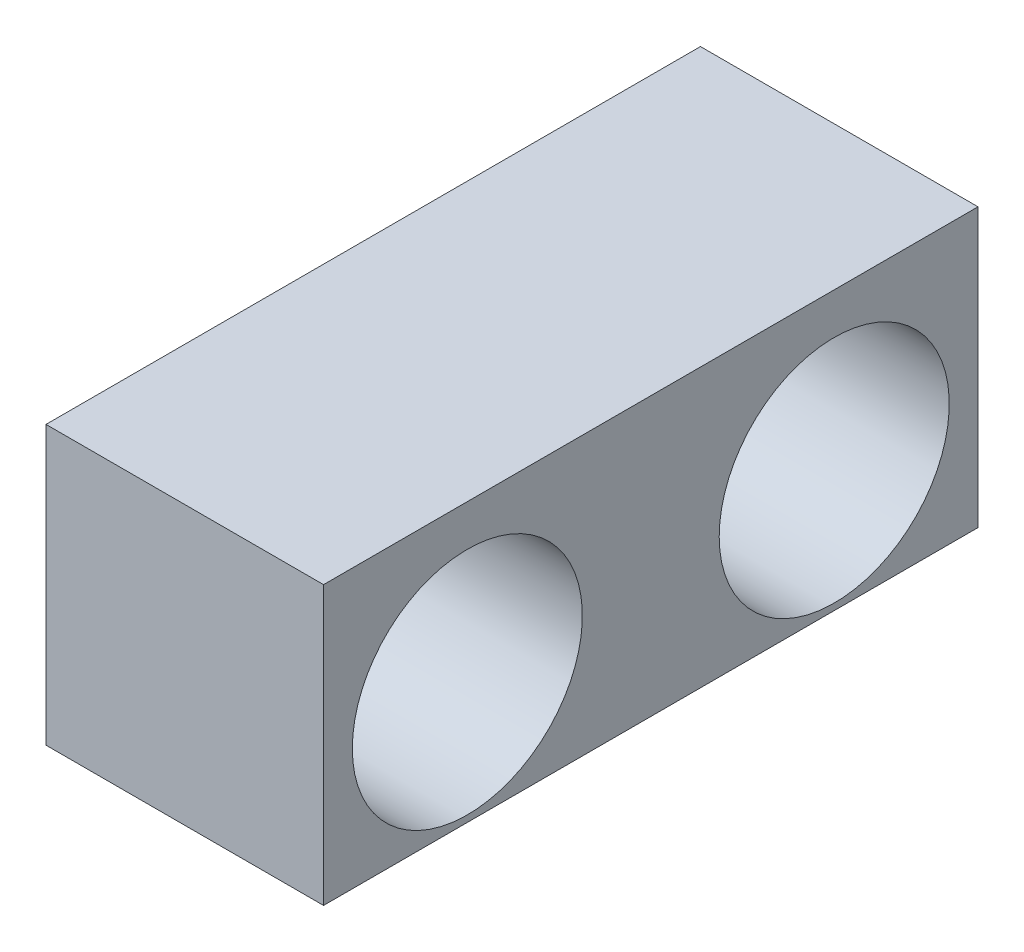
SolidWorks part; units mm, degrees
ref_plane "Front Plane" through (0, 0, 0) normal (0, 0, 1) x (1, 0, 0)
ref_plane "Top Plane" through (0, 0, 0) normal (0, 1, 0) x (1, 0, 0)
ref_plane "Right Plane" through (0, 0, 0) normal (1, 0, 0) x (0, 0, -1)
other "Lead Shot"
sketch "Sketch1" plane through (0, 0, 0) normal (0, 1, 0) x (1, 0, 0)
  circle A0 centre (0, 0) radius 75
  dimension "D1" = 150
extrude "Boss-Extrude1" add sketch "Sketch1" along normal blind 100
sketch "Sketch2" plane through (0, 100, 0) normal (0, 1, 0) x (1, 0, 0)
  line L1 (-22.2, -52.3449) -> (-22.2, 52.3449) construction
  line L3 (-22.2, -52.3449) -> (-22.2, 52.3449)
  line L4 (22.2, 52.3449) -> (22.2, -52.3449) construction
  line L5 (22.2, 52.3449) -> (22.2, -52.3449)
  line L6 (-22.2, -52.3449) -> (22.2, -52.3449)
  line L7 (-22.2, 52.3449) -> (22.2, 52.3449)
extrude "Cut-Extrude1" cut sketch "Sketch2" against normal through all flip side to cut
sketch "Sketch3" plane through (0, 0, 52.3449) normal (0, 0, 1) x (1, 0, 0)
  line L0 (-28.2, 44.4449) -> (-22.2, 44.4449) construction
  line L1 (-28.2, 44.4449) -> (-22.2, 44.4449) construction
  line L3 (-22.2, 44.4449) -> (22.2, 44.4449)
  line L4 (-22.2, 44.4449) -> (-22.2, 100)
  line L5 (-22.2, 100) -> (22.2, 100)
  line L6 (22.2, 44.4449) -> (22.2, 100)
extrude "Cut-Extrude2" cut sketch "Sketch3" against normal through all
sketch "Sketch4" plane through (-22.2, 0, 0) normal (-1, 0, 0) x (0, 0, 1)
  circle A0 centre (29.3449, 19.4449) radius 18.4 construction
  circle A1 centre (-29.3449, 19.4449) radius 18.4 construction
  circle A2 centre (29.3449, 19.4449) radius 18.4
  circle A3 centre (-29.3449, 19.4449) radius 18.4
extrude "Cut-Extrude3" cut sketch "Sketch4" against normal through all
